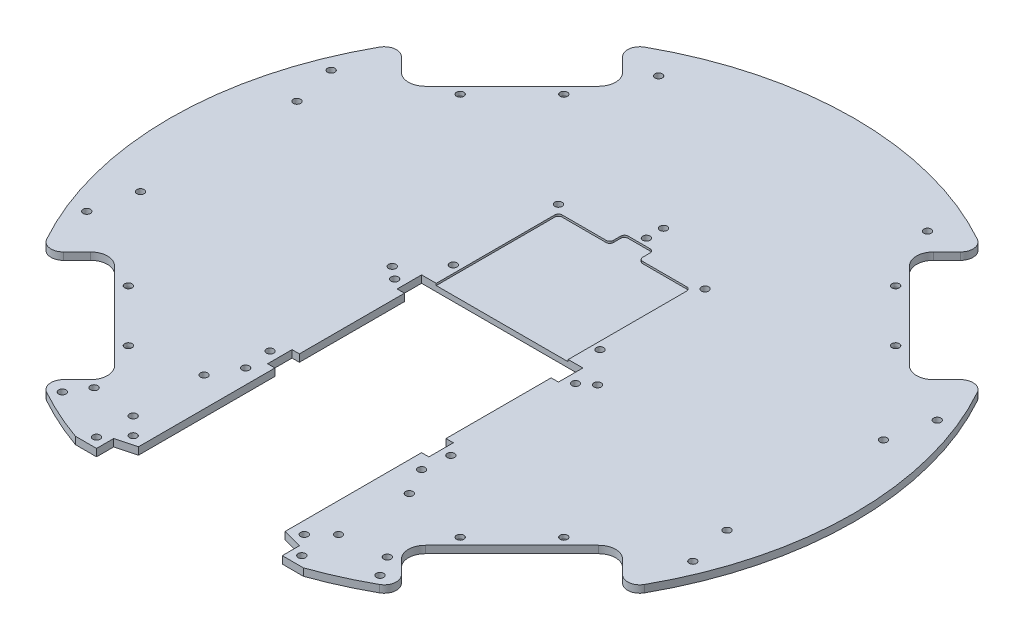
SolidWorks part; units mm, degrees
material "1060 Alloy"
ref_plane "Front Plane" through (0, 0, 0) normal (0, 0, 1) x (1, 0, 0)
ref_plane "Top Plane" through (0, 0, 0) normal (0, 1, 0) x (1, 0, 0)
ref_plane "Right Plane" through (0, 0, 0) normal (1, 0, 0) x (0, 0, -1)
sketch "Sketch1" plane through (0, 0, 0) normal (0, 1, 0) x (1, 0, 0)
  circle A0 centre (0, 0) radius 140
  dimension "D1" = 280
extrude "Boss-Extrude1" add sketch "Sketch1" along normal blind 3
sketch "Sketch7" plane through (0, 3, 0) normal (0, 1, 0) x (1, 0, 0)
  line L0 (-99.0303, -63.6043) -> (-63.6043, -99.0303)
  line L1 (-108.8591, -63.6043) -> (-121.6224, -76.3675)
  line L2 (-63.6043, -108.8591) -> (-76.3675, -121.6224)
  line L3 (-121.6224, -76.3675) -> (-76.3675, -121.6224)
  line L4 (0, 0) -> (-98.9949, -98.9949) construction
  line L7 (0, 0) -> (0, 130) construction
  circle A0 centre (0, 0) radius 140 construction
  arc A1 (-108.8591, -63.6043) -> (-99.0303, -63.6043) centre (-103.9447, -68.5186) cw
  arc A2 (-63.6043, -99.0303) -> (-63.6043, -108.8591) centre (-68.5186, -103.9447) cw
  dimension "D4" = 6.95
  dimension "D1" = 115
  dimension "D2" = 64
  dimension "D3" = 135
extrude "Cut-Extrude4" cut sketch "Sketch7" against normal up to next
sketch "Sketch9" plane through (0, 3, 0) normal (0, 1, 0) x (1, 0, 0)
  line L1 (-63.6043, -99.0303) -> (-99.0303, -63.6043) construction
  line L4 (-108.8591, -63.6043) -> (-119.0017, -73.7469) construction
  circle A0 centre (-89.0955, -67.8823) radius 1.5
  circle A1 centre (-67.8823, -89.0955) radius 1.5
  dimension "D4" = 3
  dimension "D1" = 4
  dimension "D2" = 30
  dimension "D3" = 17
  dimension "D5" = 4
extrude "Cut-Extrude6" cut sketch "Sketch9" against normal up to next
fillet "Fillet1" radius 5 2 edges at (-73.7469, 1.5, 119.0017) (-119.0017, 1.5, 73.7469)
pattern_circular "CirPattern1" count 4 over 360 about axis through (0, 3, 0) along (0, 1, 0) of "Cut-Extrude4", "Fillet1", "Cut-Extrude6"
sketch "Sketch2" plane through (0, 3, 0) normal (0, 1, 0) x (1, 0, 0)
  line L0 (-46.6476, -132) -> (-38, -132)
  line L1 (-30, -122.8564) -> (-30, -67)
  line L2 (-33, -4) -> (33, -4)
  line L3 (30, -67) -> (30, -122.8564)
  line L4 (38, -132) -> (46.6476, -132)
  line L5 (46.6476, -132) -> (46.6476, -140)
  line L6 (46.6476, -140) -> (-46.6476, -140)
  line L7 (-46.6476, -140) -> (-46.6476, -132)
  line L8 (-33, -57) -> (-33, -67)
  line L9 (-33, -67) -> (-30, -67)
  line L10 (33, -57) -> (33, -67)
  line L11 (33, -67) -> (30, -67)
  line L12 (-33, -57) -> (-30, -57)
  line L13 (-30, -57) -> (-30, -14)
  line L14 (-30, -14) -> (-33, -14)
  line L15 (-33, -14) -> (-33, -4)
  line L16 (33, -4) -> (33, -14)
  line L17 (33, -14) -> (30, -14)
  line L18 (30, -14) -> (30, -57)
  line L19 (30, -57) -> (33, -57)
  line L20 (-38, -132) -> (-38, -125)
  line L21 (-38, -125) -> (-30, -122.8564)
  line L22 (38, -132) -> (38, -125)
  line L23 (38, -125) -> (30, -122.8564)
  circle A0 centre (0, 0) radius 140 construction
  dimension "D8" = 3
  dimension "D5" = 63
  dimension "D6" = 66
  dimension "D1" = 8
  dimension "D2" = 65
  dimension "D3" = 60
  dimension "D4" = 16.6476
  dimension "D7" = 10
  dimension "D9" = 76
  dimension "D10" = 7
  dimension "D11" = 105
extrude "Cut-Extrude1" cut sketch "Sketch2" against normal up to next
fillet "Fillet3" radius 1.5 8 edges at (67.8823, 0, 90.5955) (89.0955, 0, 69.3823) (89.0955, 0, -66.3823) (67.8823, 0, -87.5955) (-67.8823, 0, -87.5955) (-89.0955, 0, -66.3823) (-67.8823, 0, 90.5955) (-89.0955, 0, 69.3823)
sketch "Sketch10" plane through (0, 3, 0) normal (0, 1, 0) x (1, 0, 0)
  line L0 (-33, -57) -> (-33, -67) construction
  line L1 (33, -67) -> (33, -57) construction
  line L2 (-33, -67) -> (-30, -67) construction
  line L4 (-30, -14) -> (-33, -14) construction
  line L5 (33, -4) -> (-33, -4) construction
  circle A0 centre (-37, -62) radius 1.5
  circle A1 centre (37, -62) radius 1.5
  circle A2 centre (-37, -11) radius 1.5
  circle A3 centre (37, -11) radius 1.5
  circle A4 centre (-42, -7) radius 1.5
  circle A5 centre (42, -7) radius 1.5
  point P17 (-31.5, -14)
  dimension "D3" = 3
  dimension "D1" = 4
  dimension "D2" = 4
  dimension "D4" = 5
  dimension "D5" = 3
  dimension "D6" = 3
  dimension "D7" = 5
  dimension "D8" = 5
extrude "Cut-Extrude7" cut sketch "Sketch10" against normal up to next
sketch "Sketch13" plane through (0, 3, 0) normal (0, 1, 0) x (1, 0, 0)
  line L0 (-38, -132) -> (-46.6476, -132) construction
  line L1 (-38, -132) -> (-46.6476, -132) construction
  circle A0 centre (-42, -84) radius 1.5
  circle A1 centre (-42, -113) radius 1.5
  circle A2 centre (42, -113) radius 1.5
  circle A3 centre (42, -84) radius 1.5
  dimension "D1" = 3
  dimension "D2" = 19
  dimension "D3" = 48
  dimension "D4" = 42
  dimension "D5" = 42
extrude "Cut-Extrude9" cut sketch "Sketch13" against normal up to next
sketch "Sketch16" plane through (0, 3, 0) normal (0, 1, 0) x (1, 0, 0)
  circle A0 centre (0, 62) radius 1.5
  circle A4 centre (0, 55) radius 1.5
  dimension "D2" = 3
  dimension "D5" = 3
  dimension "D1" = 62
  dimension "D7" = 55
extrude "Cut-Extrude12" cut sketch "Sketch16" against normal up to next
sketch "Sketch17" plane through (0, 3, 0) normal (0, 1, 0) x (1, 0, 0)
  circle A0 centre (-124, 50) radius 1.5
  circle A1 centre (-124, -50) radius 1.5
  circle A2 centre (124, 50) radius 1.5
  circle A3 centre (124, -50) radius 1.5
  dimension "D1" = 3
  dimension "D2" = 50
  dimension "D3" = 50
  dimension "D4" = 124
  dimension "D5" = 124
extrude "Cut-Extrude13" cut sketch "Sketch17" against normal up to next
sketch "Sketch18" plane through (0, 3, 0) normal (0, 1, 0) x (1, 0, 0)
  line L1 (-27, -4) -> (27, -4)
  line L2 (-27, -4) -> (-27, 46)
  line L3 (-27, 46) -> (27, 46)
  line L4 (27, -4) -> (27, 46)
  line L5 (33, -4) -> (-33, -4) construction
  dimension "D1" = 50
  dimension "D2" = 54
  dimension "D3" = 27
extrude "Cut-Extrude14" cut sketch "Sketch18" against normal blind 0.8
sketch "Sketch19" plane through (0, 3, 0) normal (0, 1, 0) x (1, 0, 0)
  line L0 (-38, -125) -> (-38, -132) construction
  line L1 (-38, -132) -> (-46.6476, -132) construction
  line L2 (38, -132) -> (38, -125) construction
  circle A0 centre (-42, -128) radius 1.5
  circle A1 centre (42, -128) radius 1.5
  dimension "D4" = 3
  dimension "D1" = 4
  dimension "D2" = 4
  dimension "D3" = 4
extrude "Cut-Extrude15" cut sketch "Sketch19" against normal up to next
sketch "Sketch20" plane through (0, 3, 0) normal (0, 1, 0) x (1, 0, 0)
  line L0 (27, 46) -> (-27, 46) construction
  line L1 (-6, 46) -> (6, 46)
  line L2 (-6, 46) -> (-6, 52)
  line L3 (-6, 52) -> (6, 52)
  line L4 (6, 46) -> (6, 52)
  circle A0 centre (0, 55) radius 1.5 construction
  dimension "D1" = 12
  dimension "D2" = 6
  dimension "D3" = 3
extrude "Cut-Extrude16" cut sketch "Sketch20" against normal up to surface (0.8 mm away) up to face at (0, 2.2, -21)
fillet "Fillet4" radius 1.5 6 edges at (6, 2.6, -46) (27, 2.6, -46) (-27, 2.6, -46) (-6, 2.6, -46) (6, 2.6, -52) (-6, 2.6, -52)
sketch "Sketch21" plane through (0, 3, 0) normal (0, 1, 0) x (1, 0, 0)
  circle A0 centre (-35, -120) radius 1.5
  circle A1 centre (-36, -73) radius 1.5
  circle A2 centre (35, -120) radius 1.5
  circle A3 centre (36, -73) radius 1.5
  circle A4 centre (-42, -128) radius 1.5 construction
  circle A5 centre (42, -128) radius 1.5 construction
  dimension "D1" = 7
  dimension "D3" = 3
  dimension "D2" = 8
  dimension "D4" = 47
  dimension "D5" = 1
  dimension "D6" = 1
  dimension "D7" = 7
extrude "Cut-Extrude17" cut sketch "Sketch21" against normal up to next
sketch "Sketch22" plane through (0, 3, 0) normal (0, 1, 0) x (1, 0, 0)
  circle A0 centre (120, 32) radius 1.5
  circle A1 centre (120, -32) radius 1.5
  circle A2 centre (-120, 32) radius 1.5
  circle A3 centre (-120, -32) radius 1.5
  dimension "D1" = 3
  dimension "D2" = 120
  dimension "D3" = 32
  dimension "D4" = 32
  dimension "D5" = 120
extrude "Cut-Extrude18" cut sketch "Sketch22" against normal up to next
sketch "Sketch23" plane through (0, 3, 0) normal (0, 1, 0) x (1, 0, 0)
  circle A0 centre (-55, 115) radius 1.5
  circle A1 centre (55, 115) radius 1.5
  dimension "D1" = 3
  dimension "D2" = 55
  dimension "D3" = 115
  dimension "D4" = 55
extrude "Cut-Extrude19" cut sketch "Sketch23" against normal up to next
sketch "Sketch24" plane through (0, 3, 0) normal (0, 1, 0) x (1, 0, 0)
  line L0 (-27, 44.5) -> (-27, -4) construction
  line L1 (-7.5, 46) -> (-25.5, 46) construction
  line L2 (-27, -4) -> (-33, -4) construction
  line L3 (27, -4) -> (27, 44.5) construction
  circle A0 centre (-30, 6) radius 1.5
  circle A1 centre (30, 6) radius 1.5
  circle A2 centre (30, 49) radius 1.5
  circle A3 centre (-30, 49) radius 1.5
  dimension "D1" = 3
  dimension "D2" = 3
  dimension "D3" = 3
  dimension "D4" = 10
  dimension "D5" = 3
extrude "Cut-Extrude20" cut sketch "Sketch24" against normal up to next
sketch "Sketch25" plane through (0, 3, 0) normal (0, 1, 0) x (1, 0, 0)
  circle A0 centre (-65, -119) radius 1.5
  circle A1 centre (-60, -111) radius 1.5
  circle A2 centre (60, -111) radius 1.5
  circle A3 centre (65, -119) radius 1.5
  dimension "D3" = 3
  dimension "D1" = 111
  dimension "D2" = 60
  dimension "D4" = 8
  dimension "D5" = 5
  dimension "D6" = 5
  dimension "D7" = 60
extrude "Cut-Extrude21" cut sketch "Sketch25" against normal up to next
